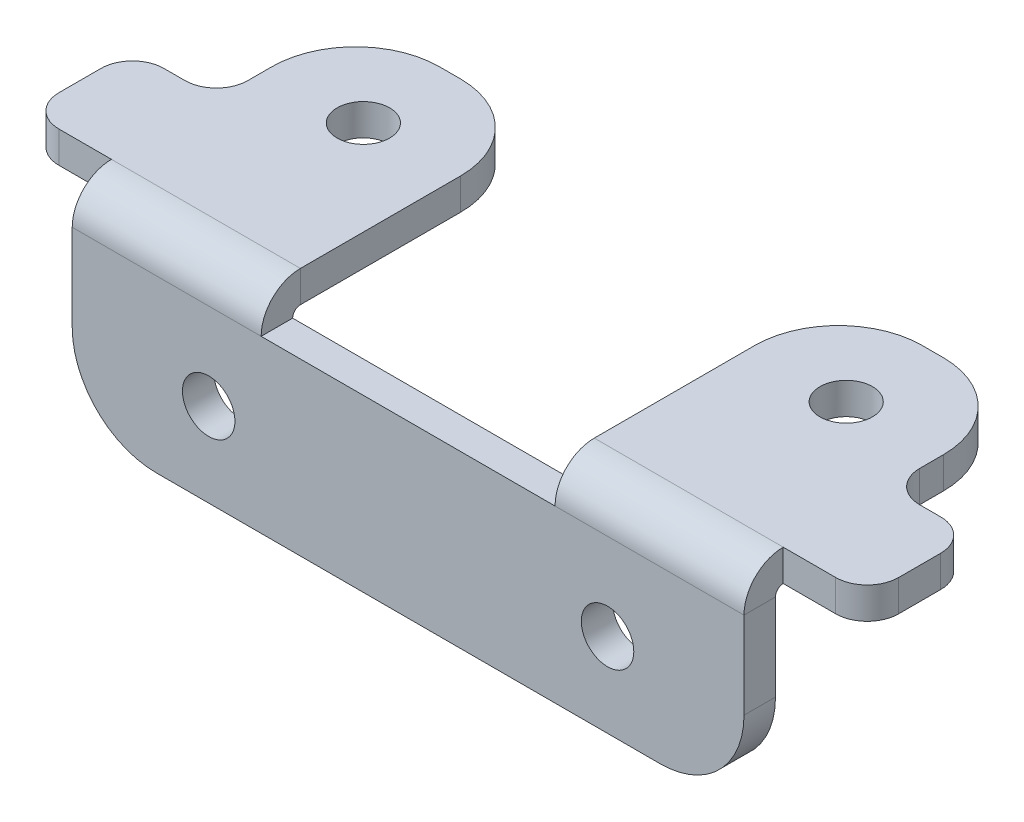
SolidWorks part; units mm, degrees
note: The reader was unsure of these and kept them because the rebuilt part matched: flange length of "Edge-Flange1".
ref_plane "Front Plane" through (0, 0, 0) normal (0, 0, 1) x (1, 0, 0)
ref_plane "Top Plane" through (0, 0, 0) normal (0, 1, 0) x (1, 0, 0)
ref_plane "Right Plane" through (0, 0, 0) normal (1, 0, 0) x (0, 0, -1)
sketch "Sketch2" plane through (0, 0, 0) normal (0, 0, 1) x (1, 0, 0)
  line L1 (-32, -8.13) -> (32, -8.13)
  line L2 (-32, -8.13) -> (-32, 8.13)
  line L3 (-32, 8.13) -> (32, 8.13)
  line L4 (32, -8.13) -> (32, 8.13)
  line L5 (-32, -8.13) -> (32, 8.13) construction
  line L6 (-32, 8.13) -> (32, -8.13) construction
  point P0 (0, 0)
  dimension "D1" = 64
  dimension "D2" = 16.26
base flange "Base-Flange1" sketch "Sketch2" thickness 3 reverse thickness direction no parameters "D1"=0.7366
edge flange "Edge-Flange1" sketch "Sketch9" flange angle 90 flange length 27 flange position bend outside bend radius 0.7366 thickness 3 relief rectangular parameters "D6"=10
sketch "Sketch9" plane through (0, 8.13, -3) normal (0, 1, 0) x (1, 0, 0)
  line L0 (14, 0) -> (14, 24)
  line L3 (14, 24) -> (32, 24)
  line L4 (32, 24) -> (32, 0)
  line L7 (0, -4.65) -> (0, -1.35) construction
  line L11 (32, 0) -> (-32, 0) construction
  line L12 (32, 0) -> (14, 0)
  point P6 (0, 0)
  point P12 (0, 0)
  dimension "D1" = 14
  dimension "D4" = 24
bend "EdgeBend1" bend radius 0.7366 bend angle 90 parameters "D5"=1
sketch "Sketch10" plane through (0, 0, 0) normal (0, 0, 1) x (1, 0, 0)
  line L0 (-19, -0.13) -> (19, -0.13) construction
  line L3 (-32, -8.13) -> (32, -8.13) construction
  circle A0 centre (-19, -0.13) radius 2.5
  circle A1 centre (19, -0.13) radius 2.5
  point P4 (0, -0.13)
  dimension "D2" = 5
  dimension "D3" = 5
  dimension "D1" = 38
  dimension "D4" = 8
extrude "Cut-Extrude1" cut sketch "Sketch10" against normal up to surface (3 mm away) normal cut yes up to face at (2.8, 1.626, -3)
fillet "Fillet1" radius 8 2 edges at (-32, -8.13, -1.5) (32, -8.13, -1.5)
sketch "Sketch14" plane through (0, 11.8666, 0) normal (0, 1, 0) x (1, 0, 0)
  line L0 (32, 3.7366) -> (14, 3.7366) construction
  circle A0 centre (23, 18.7366) radius 2.5
  circle A1 centre (37, 22) radius 1
  dimension "D2" = 5
  dimension "D3" = 2
  dimension "D1" = 15
extrude "Cut-Extrude5" cut sketch "Sketch14" against normal up to surface (3 mm away) normal cut yes up to face at (23, 8.8666, -15.3683)
sketch "Sketch15" plane through (0, 11.8666, 0) normal (0, 1, 0) x (1, 0, 0)
  line L1 (32, 3.7366) -> (40, 3.7366)
  line L2 (32, 3.7366) -> (32, 13.7366)
  line L3 (32, 13.7366) -> (40, 13.7366)
  line L4 (40, 3.7366) -> (40, 13.7366)
  dimension "D1" = 8
  dimension "D2" = 10
base flange "Tab1" sketch "Sketch15" thickness 3 reverse thickness direction no parameters "D1"=0.7366
fillet "Fillet4" radius 8 2 edges at (32, 10.3666, -27) (14, 10.3666, -27)
fillet "Fillet5" radius 3 3 edges at (32, 10.3666, -13.7366) (40, 10.3666, -13.7366) (40, 10.3666, -3.7366)
mirror "Mirror1" about plane through (0, 0, 0) normal (1, 0, 0) of "Edge-Flange1", "Tab1", "Cut-Extrude5", "Fillet5", "Fillet4"
bend "MirrorBend1" bend radius 0.7366 bend angle 90 parameters "D5"=2
sketch "Bend-Lines1" [suppressed] plane through (0, 0, 0) normal (0, 1, 0) x (1, 0, 0)
sketch "Bounding-Box1" [suppressed] plane through (0, 0, 0) normal (0, 1, 0) x (1, 0, 0)
sheet metal parameters "Sheet-Metal1" thickness 3 parameters "D1"=0.7366
flat pattern "Flat-Pattern1" [suppressed]
sketch "Bend-Lines2" plane through (0, 0, 0) normal (0, 1, 0) x (1, 0, 0)
sketch3d "Bounding-Box2" [suppressed]
  line L0 (-32, -8.13, 0) -> (32, -8.13, 0) construction
  line L1 (-32, 8.13, 0) -> (32, 8.13, 0) construction
  line L2 (-32, -8.13, 0) -> (-32, 8.13, 0) construction
  line L3 (32, -8.13, 0) -> (32, 8.13, 0) construction
sheet metal parameters "Sheet-Metal2" thickness 3 parameters "D1"=0.7366
flat pattern "Flat-Pattern1"
sketch "Bend-Lines2" plane through (0, 0, 0) normal (0, 0, 1) x (1, 0, 0)
  line L0 (32, 9.8866) -> (-32, 9.8866) construction
  line L1 (32, 9.8866) -> (-32, 9.8866) construction
sketch3d "Bounding-Box2" [suppressed]
  line L0 (-32, -8.13, 0) -> (32, -8.13, 0) construction
  line L1 (-32, 34.6466, 0) -> (32, 34.6466, 0) construction
  line L2 (-32, -8.13, 0) -> (-32, 34.6466, 0) construction
  line L3 (32, -8.13, 0) -> (32, 34.6466, 0) construction
bend of the flat pattern "Flatten-<EdgeBend1>1"
sheet metal parameters "Sheet-Metal3" thickness 3 parameters "D1"=0.7366
flat pattern "Flat-Pattern1" [suppressed]
sketch "Bend-Lines2" plane through (0, 0, 0) normal (0, 0, 1) x (1, 0, 0)
  point P0 (32, 9.8866)
  point P1 (14, 9.8866)
sketch3d "Bounding-Box2" [suppressed]
  line L0 (-32, -8.13, 0) -> (32, -8.13, 0) construction
  line L1 (-32, 8.13, 0) -> (32, 8.13, 0) construction
  line L2 (-32, -8.13, 0) -> (-32, 8.13, 0) construction
  line L3 (32, -8.13, 0) -> (32, 8.13, 0) construction
bend of the flat pattern "Flatten-<EdgeBend1>1"
sheet metal parameters "Sheet-Metal6" thickness 3 parameters "D1"=0.7366
flat pattern "Flat-Pattern1"
sketch "Bend-Lines2" plane through (0, 0, 0) normal (0, 0, 1) x (1, 0, 0)
  line L0 (32, 9.8866) -> (14, 9.8866) construction
  line L1 (32, 9.8866) -> (14, 9.8866) construction
sketch3d "Bounding-Box2" [suppressed]
  line L0 (-32, 34.9066, 0) -> (32, 34.9066, 0) construction
  line L1 (-32, -8.13, 0) -> (32, -8.13, 0) construction
  line L2 (-32, 34.9066, 0) -> (-32, -8.13, 0) construction
  line L3 (32, 34.9066, 0) -> (32, -8.13, 0) construction
bend of the flat pattern "Flatten-<EdgeBend1>1"
sheet metal parameters "Sheet-Metal7" thickness 3 parameters "D1"=0.7366
flat pattern "Flat-Pattern8"
sketch "Bend-Lines3" plane through (0, 0, 0) normal (0, 0, 1) x (1, 0, 0)
  line L0 (32, 9.8866) -> (14, 9.8866) construction
  line L1 (32, 9.8866) -> (14, 9.8866) construction
  line L2 (-14, 9.8866) -> (-32, 9.8866) construction
  line L3 (-14, 9.8866) -> (-32, 9.8866) construction
sketch3d "Bounding-Box3" [suppressed]
  line L0 (-40, -8.13, 0) -> (40, -8.13, 0) construction
  line L1 (-40, 34.9066, 0) -> (40, 34.9066, 0) construction
  line L2 (-40, -8.13, 0) -> (-40, 34.9066, 0) construction
  line L3 (40, -8.13, 0) -> (40, 34.9066, 0) construction
bend of the flat pattern "Flatten-<EdgeBend1>1"
bend of the flat pattern "Flatten-<MirrorBend1>1"
sheet metal parameters "Sheet-Metal8" thickness 3 parameters "D1"=0.7366
flat pattern "Flat-Pattern8"
sketch "Bend-Lines3" plane through (0, 0, 0) normal (0, 0, 1) x (1, 0, 0)
  line L0 (32, 9.8866) -> (14, 9.8866) construction
  line L1 (32, 9.8866) -> (14, 9.8866) construction
sketch3d "Bounding-Box3" [suppressed]
  line L0 (-17.4146, -30.4259, 0) -> (48.2428, 3.3423, 0) construction
  line L1 (-36.1472, 5.997, 0) -> (29.5102, 39.7652, 0) construction
  line L2 (-17.4146, -30.4259, 0) -> (-36.1472, 5.997, 0) construction
  line L3 (48.2428, 3.3423, 0) -> (29.5102, 39.7652, 0) construction
bend of the flat pattern "Flatten-<EdgeBend1>2"
